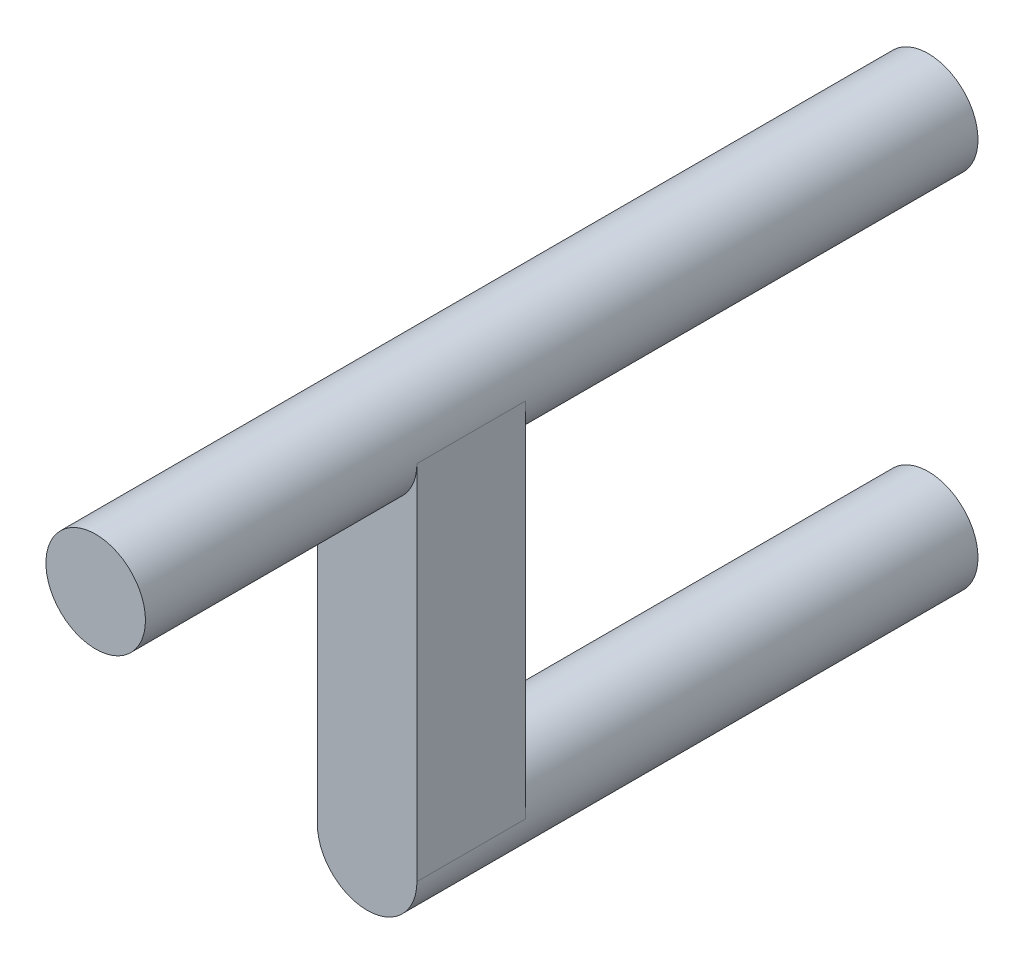
SolidWorks part; units mm, degrees
ref_plane "Front Plane" through (0, 0, 0) normal (0, 0, 1) x (1, 0, 0)
ref_plane "Top Plane" through (0, 0, 0) normal (0, 1, 0) x (1, 0, 0)
ref_plane "Right Plane" through (0, 0, 0) normal (1, 0, 0) x (0, 0, -1)
sketch "Sketch2" plane through (0, 0, 0) normal (0, 0, 1) x (1, 0, 0)
  line L0 (0, 0) -> (0, -50.8)
  circle A0 centre (0, 0) radius 6.985
  circle A1 centre (0, -50.8) radius 6.985
  dimension "D1" = 13.97
  dimension "D2" = 13.97
extrude "Boss-Extrude11" add sketch "Sketch2" along normal blind 116.84 contours A0 region at (-4.7994, 4.7994, 0)
extrude "Boss-Extrude12" add sketch "Sketch2<4>" along normal blind 63.5 separate body contours A1 region at (4.7994, -46.0006, 0)
sketch "Sketch2<4>" plane through (0, 0, 0) normal (0, 0, 1) x (1, 0, 0) same geometry as "Sketch2"
sketch "Sketch19" plane through (0, 0, 63.5) normal (0, 0, 1) x (1, 0, 0)
  line L0 (-6.985, 0) -> (-6.985, -50.8)
  line L1 (6.985, 0) -> (6.985, -50.8)
  line L2 (6.985, -50.8) -> (-6.985, -50.8)
  line L3 (-6.985, 0) -> (6.985, 0)
  circle A0 centre (0, 0) radius 6.985 construction
  circle A1 centre (0, -50.8) radius 6.985 construction
extrude "Boss-Extrude13" add sketch "Sketch19" along normal blind 15.24
sketch "Sketch20" plane through (0, 0, 63.5) normal (0, 0, 1) x (1, 0, 0)
  line L0 (-6.985, -50.8) -> (6.985, -50.8) construction
  circle A0 centre (0, -50.8) radius 7.62
sketch "Sketch21" plane through (0, 0, 63.5) normal (0, 0, 1) x (1, 0, 0)
  circle A0 centre (0, -50.8) radius 6.985
extrude "Boss-Extrude15" add sketch "Sketch21" along normal blind 15.24
